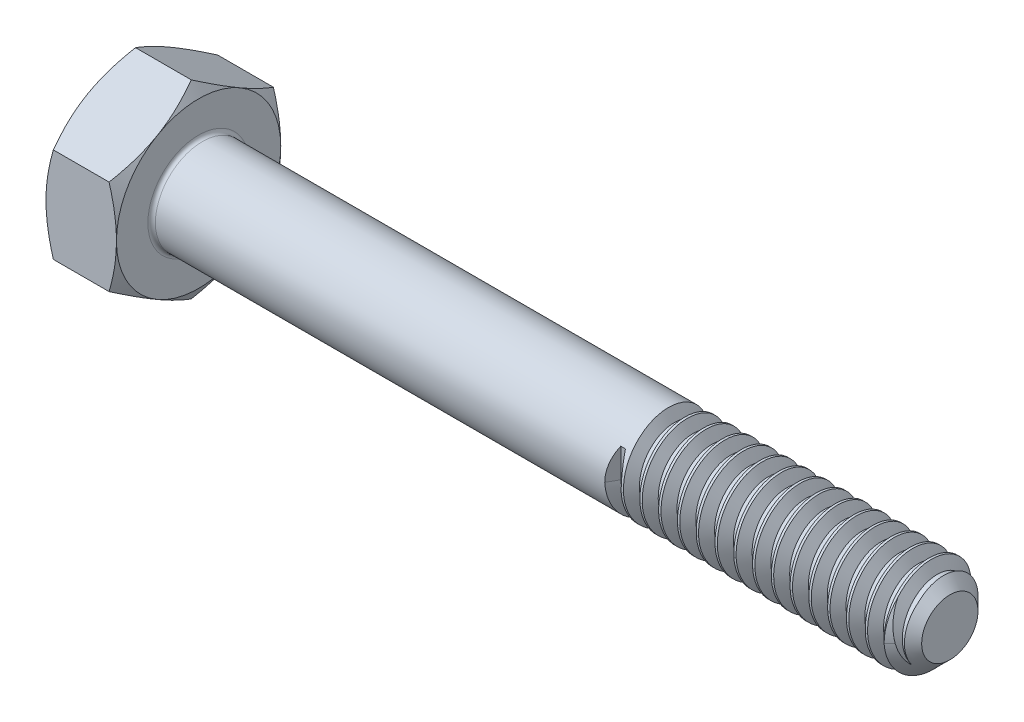
SolidWorks part; units mm, degrees
material "Plain Carbon Steel"
ref_plane "Front Plane" through (0, 0, 0) normal (0, 0, 1) x (1, 0, 0)
ref_plane "Top Plane" through (0, 0, 0) normal (0, 1, 0) x (1, 0, 0)
ref_plane "Right Plane" through (0, 0, 0) normal (1, 0, 0) x (0, 0, -1)
sketch "Sketch1" plane through (0, 0, 0) normal (0, 0, 1) x (1, 0, 0)
  line L0 (0, 0) -> (55.5625, 0) construction
  line L1 (55.5625, 0) -> (55.5625, 1.905)
  line L2 (54.2925, 3.175) -> (4.7625, 3.175)
  line L3 (4.7625, 3.175) -> (4.7625, 6.4158) construction
  line L4 (4.7625, 6.4158) -> (0, 6.4158) construction
  line L5 (0, 6.4158) -> (0, 0) construction
  line L6 (55.5625, 1.905) -> (54.2925, 3.175)
  line L7 (0, 6.4158) -> (-5.5563, 3.2079) construction
  line L8 (-5.5563, 3.2079) -> (-5.5563, -3.2079) construction
  line L9 (-5.5563, -3.2079) -> (0, -6.4158) construction
  line L10 (0, -6.4158) -> (5.5562, -3.2079) construction
  line L11 (5.5562, -3.2079) -> (5.5562, 3.2079) construction
  line L12 (5.5562, 3.2079) -> (0, 6.4158) construction
  line L13 (0, 5.5562) -> (0.4963, 6.4158)
  line L14 (4.2662, 6.4158) -> (4.7625, 5.5562)
  line L15 (0, 0) -> (0, 5.5562)
  line L16 (0.4963, 6.4158) -> (4.2662, 6.4158)
  line L17 (4.7625, 3.175) -> (4.7625, 5.5562)
  line L18 (0, 0) -> (55.5625, 0)
  circle A0 centre (0, 0) radius 5.5562 construction
  point P4 (55.5625, 3.175)
  dimension "D4" = 11.1125
  dimension "D1" = 6.35
  dimension "D2" = 50.8
  dimension "D3" = 4.7625
  dimension "D5" = 30
revolve "Revolve1" add sketch "Sketch1" angle 360 about L18
sketch "Sketch2" plane through (0, 0, 0) normal (-1, 0, 0) x (0, 0, 1)
  line L1 (0, 6.4158) -> (-5.5563, 3.2079)
  line L2 (-5.5563, 3.2079) -> (-5.5562, -3.2079)
  line L3 (-5.5562, -3.2079) -> (0, -6.4158)
  line L4 (0, -6.4158) -> (5.5563, -3.2079)
  line L5 (5.5563, -3.2079) -> (5.5562, 3.2079)
  line L6 (5.5562, 3.2079) -> (0, 6.4158)
  circle A0 centre (0, 0) radius 5.5563 construction
extrude "Cut-Extrude1" cut sketch "Sketch2" against normal through all flip side to cut
thread "Thread1" pitch 1.27 method cut profile "Thread Profile1" start angle 0, offset 2.54, length 21.59, pitch 1.27, diameter 6.35
ref_plane "Plane1" through (58.1025, 0, 3.175) normal (0, -1, 0) x (0, 0, 1)
sketch "Thread Profile1" plane through (58.1025, 0, 3.175) normal (0, -1, 0) x (0, 0, 1)
  line L0 (0, 0) -> (0, 1.27) construction
  line L11 (0, 0) -> (0, 1.1112)
  line L12 (0, 1.1112) -> (-0.6874, 0.7144)
  line L13 (-0.6874, 0.7144) -> (-0.6874, 0.3969)
  line L15 (-0.6874, 0.3969) -> (0, 0)
  line L17 (-0.6874, 0.5556) -> (0, 0.5556) construction
  point P2 (0, 0)
  dimension "Pitch" = 1.27
  dimension "Profile_Angle" = 60
  dimension "Profile_Land" = 0.3175
  dimension "Profile_Height" = 0.6874
sketch "Sketch7" plane through (0, 0, 0) normal (0, -1, 0) x (1, 0, 0)
  line L4 (36.1156, 2.4876) -> (36.5125, 3.175)
  line L5 (36.5125, 3.175) -> (35.4013, 3.175)
  line L6 (35.4013, 3.175) -> (35.7981, 2.4876)
  line L7 (35.7981, 2.4876) -> (36.1156, 2.4876)
  line L8 (36.1156, 2.4876) -> (36.5125, 3.175)
  line L9 (36.5125, 3.175) -> (35.4013, 3.175)
  line L10 (35.4013, 3.175) -> (35.7981, 2.4876)
  line L11 (35.7981, 2.4876) -> (36.1156, 2.4876)
  dimension "D1" = 0
extrude "Cut-Extrude2" cut sketch "Sketch7" against normal through all
fillet "Fillet1" radius 0.254 1 edges at (4.7625, 0, 3.175)
